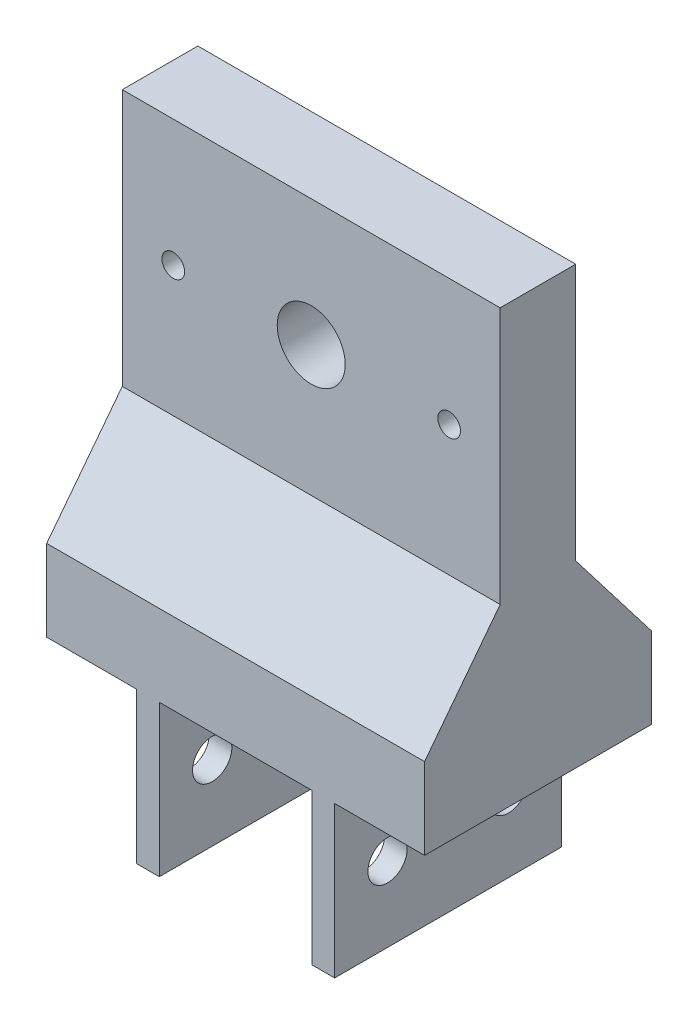
SolidWorks part; units mm, degrees
ref_plane "前视基准面" through (0, 0, 0) normal (0, 0, 1) x (1, 0, 0)
ref_plane "上视基准面" through (0, 0, 0) normal (0, 1, 0) x (1, 0, 0)
ref_plane "右视基准面" through (0, 0, 0) normal (1, 0, 0) x (0, 0, -1)
other "Configuration Table"
sketch "草图1" plane through (0, 0, 0) normal (0, 0, 1) x (1, 0, 0)
  line L0 (0, -39.6057) -> (0, 25.2485) construction
  line L9 (10.1, -25.375) -> (13.1, -25.375)
  line L10 (-25, -5.375) -> (-13.1, -5.375)
  line L11 (-25, -5.375) -> (-25, 5.375)
  line L12 (-25, 5.375) -> (25, 5.375)
  line L13 (25, -5.375) -> (25, 5.375)
  line L14 (-25, -5.375) -> (25, 5.375) construction
  line L15 (-25, 5.375) -> (25, -5.375) construction
  line L16 (-10.1, -5.375) -> (10.1, -5.375)
  line L17 (-13.1, -5.375) -> (-13.1, -25.375)
  line L18 (-13.1, -25.375) -> (-10.1, -25.375)
  line L19 (13.1, -5.375) -> (13.1, -25.375)
  line L21 (-10.1, -25.375) -> (-10.1, -5.375)
  line L22 (-10.1, -5.375) -> (10.1, -5.375)
  line L23 (10.1, -25.375) -> (10.1, -5.375)
  line L24 (-8.4435, -45.2703) -> (10.1, -5.375) construction
  line L25 (-10.1, -5.375) -> (10.5079, -49.7116) construction
  line L26 (-10.1, -5.375) -> (10.1, -5.375)
  line L27 (13.1, -5.375) -> (25, -5.375)
  point P2 (0, 0)
  point P12 (0, -27.1045)
  dimension "D1" = 50
  dimension "D2" = 10.75
  dimension "D3" = 20
  dimension "D4" = 3
  dimension "D5" = 20.2
extrude "凸台-拉伸1" add sketch "草图1" along normal blind 30 contours L19 L27 L13 L12 L11 L10 L17 L18 L21 L16 L23 L9 region at (0, -2.8061, 0)
sketch "草图2" plane through (0, 5.375, 0) normal (0, 1, 0) x (1, 0, 0)
  line L5 (-25, -30) -> (-25, 0) construction
  line L6 (-25, -10) -> (25, -10)
  line L7 (-25, -10) -> (-25, -20)
  line L8 (-25, -20) -> (25, -20)
  line L9 (25, -10) -> (25, -20)
  line L10 (25, -30) -> (25, 0) construction
  line L11 (-25, 0) -> (25, 0) construction
  dimension "D1" = 10
  dimension "D2" = 10
extrude "凸台-拉伸2" add sketch "草图2" along normal blind 50
hole_wizard "孔2" positions "草图8" profile "草图9" legacy end condition through all
sketch "草图8" plane through (-13.1, 0, 0) normal (-1, 0, 0) x (0, 0, 1)
  line L0 (30, -5.375) -> (0, -5.375) construction
  line L1 (0, -5.375) -> (0, -25.375) construction
  line L2 (30, -5.375) -> (30, -25.375) construction
  point P0 (7, -15.375)
  point P2 (23, -15.375)
  dimension "D1" = 10
  dimension "D2" = 10
  dimension "D3" = 7
  dimension "D4" = 7
sketch "草图9" plane through (-13.1, -15.375, 7) normal (0, 1, 0) x (0, 0, 1)
  line L0 (0, 0) -> (0, 38.1)
  line L1 (0, 38.1) -> (2.6, 38.1)
  line L2 (2.6, 38.1) -> (2.6, 0)
  line L3 (2.6, 0) -> (0, 0)
  line L4 (0, 110) -> (0, -10) construction
  dimension "直径" = 5.2
  dimension "深度" = 38.1
hole_wizard "孔3" positions "草图12" profile "草图13" legacy end condition through all
sketch "草图12" plane through (0, 0, 10) normal (0, 0, -1) x (-1, 0, 0)
  line L0 (0, 55.375) -> (0, 5.375) construction
  line L1 (-25, 55.375) -> (25, 55.375) construction
  line L2 (25, 5.375) -> (-25, 5.375) construction
  line L4 (-25, 5.375) -> (25, 5.375) construction
  point P0 (0, 35.625)
  dimension "D1" = 30.25
sketch "草图13" plane through (0, 35.625, 10) normal (1, 0, 0) x (0, 1, 0)
  line L0 (0, 0) -> (0, 20)
  line L1 (0, 20) -> (4.5, 20)
  line L2 (4.5, 20) -> (4.5, 0)
  line L3 (4.5, 0) -> (0, 0)
  line L4 (0, 110) -> (0, -10) construction
  dimension "直径" = 9
  dimension "深度" = 20
sketch "草图17" plane through (0, 0, 10) normal (0, 0, -1) x (-1, 0, 0)
  line L0 (0, 55.375) -> (0, 5.375) construction
  line L1 (-25, 55.375) -> (25, 55.375) construction
  line L2 (25, 5.375) -> (-25, 5.375) construction
  line L3 (-25.3813, 35.625) -> (25.3813, 35.625) construction
  circle A0 centre (18.25, 35.625) radius 2.45
  circle A1 centre (-18.25, 35.625) radius 2.45
  point P10 (0, 35.625)
  dimension "D1" = 4.9
  dimension "D2" = 4.9
  dimension "D3" = 36.5
extrude "凸台-拉伸6" add sketch "草图17" along normal blind 4
hole_wizard "孔5" positions "草图18" profile "草图19" legacy end condition through all
sketch "草图18" plane through (0, 0, 6) normal (0, 0, -1) x (-1, 0, 0)
  point P0 (18.25, 35.625)
  point P3 (-18.25, 35.625)
sketch "草图19" plane through (-18.25, 35.625, 6) normal (1, 0, 0) x (0, 1, 0)
  line L0 (0, 0) -> (0, 24)
  line L1 (0, 24) -> (1.5, 24)
  line L2 (1.5, 24) -> (1.5, 0)
  line L3 (1.5, 0) -> (0, 0)
  line L4 (0, 110) -> (0, -10) construction
  dimension "直径" = 3
  dimension "深度" = 24
sketch "草图20" plane through (-25, 0, 0) normal (-1, 0, 0) x (0, 0, 1)
  line L0 (20, 18.375) -> (30, 5.375)
  line L1 (20, 55.375) -> (20, 5.375) construction
  line L2 (30, -5.375) -> (30, 5.375) construction
  line L3 (30, 5.375) -> (20, 5.375) construction
  line L4 (30, 5.375) -> (20, 5.375)
  line L5 (20, 5.375) -> (20, 18.375)
  line L6 (10, 18.375) -> (0, 5.375)
  line L7 (10, 55.375) -> (10, 5.375) construction
  line L8 (0, 5.375) -> (10, 5.375)
  line L9 (10, 5.375) -> (10, 18.375)
  dimension "D1" = 13
extrude "凸台-拉伸7" add sketch "草图20" against normal up to surface (50 mm away) up to face at (25, 15.1875, 15)
sketch "草图21" plane through (-25, 0, 0) normal (-1, 0, 0) x (0, 0, 1)
  line L0 (10, 55.375) -> (10, 18.375) construction
  line L1 (20, 55.375) -> (10, 55.375)
  line L2 (20, 55.375) -> (20, 52.375)
  line L3 (20, 52.375) -> (10, 52.375)
  line L4 (10, 55.375) -> (10, 52.375)
  dimension "D1" = 3
extrude "切除-拉伸1" cut sketch "草图21" against normal through all
sketch "草图22" plane through (0, 0, 20) normal (0, 0, 1) x (1, 0, 0)
  circle A0 centre (0, 35.625) radius 4.5
  circle A1 centre (0, 35.625) radius 5
  dimension "D1" = 10
